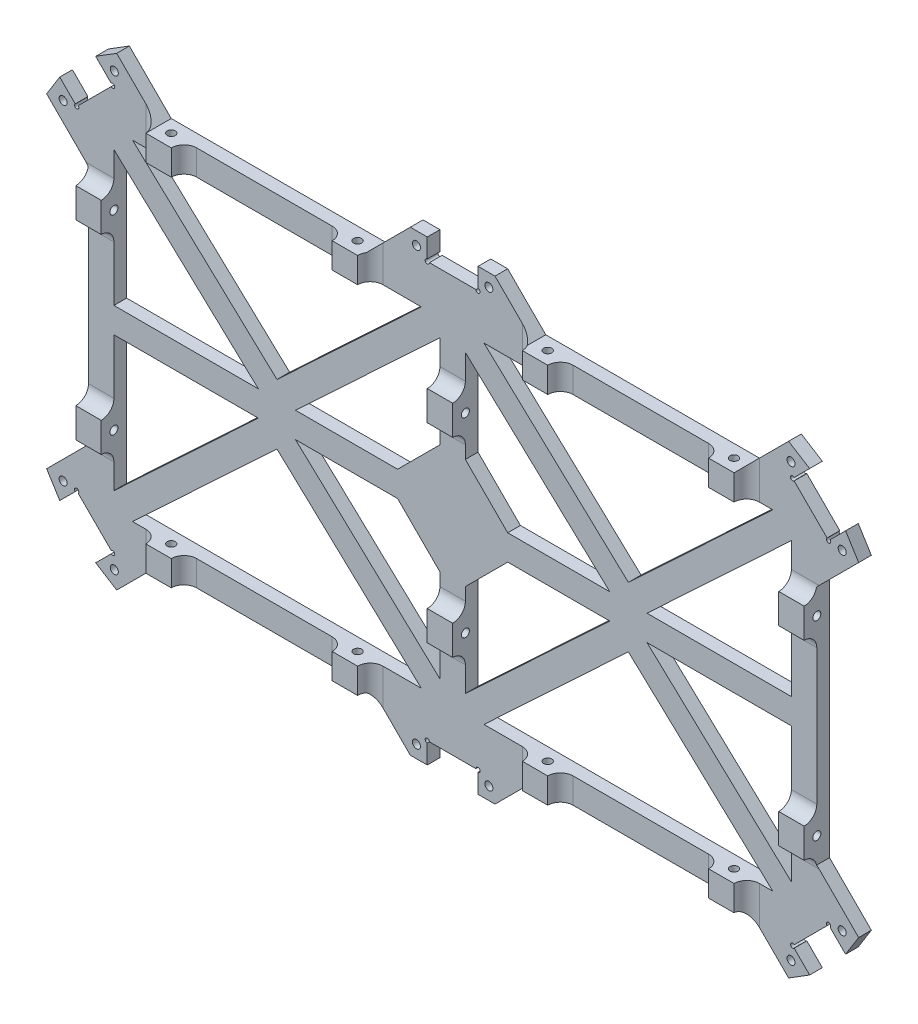
SolidWorks part; units mm, degrees
ref_plane "Plan de face" through (0, 0, 0) normal (0, 0, 1) x (1, 0, 0)
ref_plane "Plan de dessus" through (0, 0, 0) normal (0, 1, 0) x (1, 0, 0)
ref_plane "Plan de droite" through (0, 0, 0) normal (1, 0, 0) x (0, 0, -1)
sketch "Esquisse1" plane through (0, 0, 0) normal (0, 0, 1) x (1, 0, 0)
  line L0 (-86, 45) -> (86, 45)
  line L1 (-75.6076, 39) -> (-7.3924, 39)
  line L2 (-80, 34.8928) -> (-80, 3)
  line L3 (-75.6076, -39) -> (-7.3924, -39)
  line L4 (80, 34.8928) -> (80, 3)
  line L5 (86, 45) -> (86, -45)
  line L6 (-86, -45) -> (86, -45)
  line L7 (-86, 45) -> (-86, -45)
  line L8 (-80, 0) -> (80, 0) construction
  line L9 (-80, 3) -> (-45.8924, 3)
  line L10 (-3, -34.8928) -> (-3, -3)
  line L11 (0, 39) -> (0, -39) construction
  line L12 (-3, 34.8928) -> (-3, 3)
  line L13 (-37.1076, -3) -> (-3, -3)
  line L14 (-10, 45) -> (-10, 39) construction
  line L15 (10, 45) -> (10, 39) construction
  line L16 (-80, 39) -> (-41.5, 3) construction
  line L17 (-60.75, 21) -> (-58.701, 23.1913) construction
  line L18 (-58.701, 23.1913) -> (-75.6076, 39)
  line L19 (-80, -3) -> (-45.8924, -3)
  line L20 (-60.75, -21) -> (-62.799, -18.8087) construction
  line L21 (-60.75, -21) -> (-58.701, -23.1913) construction
  line L22 (-80, -39) -> (-41.5, -3) construction
  line L23 (-58.8571, 23.3372) -> (-41.5, 7.1072)
  line L24 (-60.75, 21) -> (-62.799, 18.8087) construction
  line L25 (-62.799, 18.8087) -> (-80, 34.8928)
  line L26 (-62.799, 18.8087) -> (-45.8924, 3)
  line L27 (-37.1076, 3) -> (-3, 3)
  line L28 (-62.799, -18.8087) -> (-45.8924, -3)
  line L29 (-62.799, -18.8087) -> (-80, -34.8928)
  line L30 (-58.8571, -23.3372) -> (-41.5, -7.1072)
  line L31 (-58.701, -23.1913) -> (-75.6076, -39)
  line L32 (3, 34.8928) -> (3, 3)
  line L33 (3, -34.8928) -> (3, -3)
  line L34 (80, -39) -> (41.5, -3) construction
  line L35 (60.75, -21) -> (58.701, -23.1913) construction
  line L36 (60.75, -21) -> (62.799, -18.8087) construction
  line L37 (58.701, -23.1913) -> (75.6076, -39)
  line L38 (58.8571, -23.3372) -> (41.5, -7.1072)
  line L39 (62.799, -18.8087) -> (80, -34.8928)
  line L40 (62.799, -18.8087) -> (45.8924, -3)
  line L41 (80, -3) -> (45.8924, -3)
  line L42 (37.1076, -3) -> (3, -3)
  line L43 (37.1076, 3) -> (3, 3)
  line L44 (80, 3) -> (45.8924, 3)
  line L45 (60.75, 21) -> (62.799, 18.8087) construction
  line L46 (60.75, 21) -> (58.701, 23.1913) construction
  line L47 (80, 39) -> (41.5, 3) construction
  line L48 (62.799, 18.8087) -> (45.8924, 3)
  line L49 (62.799, 18.8087) -> (80, 34.8928)
  line L50 (58.8571, 23.3372) -> (41.5, 7.1072)
  line L51 (58.701, 23.1913) -> (75.6076, 39)
  line L52 (7.3924, -39) -> (75.6076, -39)
  line L53 (7.3924, 39) -> (75.6076, 39)
  line L54 (-80, -39) -> (80, -39) construction
  line L55 (-80, -3) -> (-80, -34.8928)
  line L56 (-80, 39) -> (80, 39) construction
  line L57 (80, -3) -> (80, -34.8928)
  line L58 (-80, 39) -> (-80, -39) construction
  line L59 (-3, 39) -> (-41.5, 3) construction
  line L60 (80, 39) -> (80, -39) construction
  line L61 (-36.5997, 7.5821) -> (-34.5507, 5.3908) construction
  line L62 (-36.5997, 7.5821) -> (-38.6487, 9.7734) construction
  line L63 (-34.5507, 5.3908) -> (-3, 34.8928)
  line L64 (-34.5507, 5.3908) -> (-37.1076, 3)
  line L65 (-34.5507, 5.3908) -> (-37.1076, 3)
  line L66 (-34.5507, 5.3908) -> (-37.1076, 3)
  line L67 (-41.5, -3) -> (-3, -39) construction
  line L68 (-41.5, 7.1072) -> (-7.3924, 39)
  line L69 (-37.1076, -3) -> (-3, -34.8928)
  line L70 (41.5, -3) -> (3, -39) construction
  line L71 (41.5, -7.1072) -> (7.3924, -39)
  line L72 (-41.5, -7.1072) -> (-7.3924, -39)
  line L73 (37.1076, -3) -> (3, -34.8928)
  line L74 (3, 39) -> (41.5, 3) construction
  line L75 (41.5, 7.1072) -> (7.3924, 39)
  line L76 (34.5507, 5.3908) -> (3, 34.8928)
  line L77 (34.5507, 5.3908) -> (37.1076, 3)
  dimension "D6" = 3
  dimension "D1" = 78
  dimension "D2" = 160
  dimension "D3" = 80
  dimension "D4" = 39
  dimension "D7" = 3
  dimension "D8" = 3
  dimension "D9" = 3
  dimension "D10" = 10
  dimension "D11" = 10
  dimension "D12" = 3
  dimension "D13" = 38.5
  dimension "D14" = 3
  dimension "D15" = 3
  dimension "D5" = 6
extrude "Boss.-Extru.1" add sketch "Esquisse1" along normal blind 3 contours L0 L7 L6 L5 L55 L19 L28 L29 L52 L33 L42 L38 L37 L31 L30 L13 L10 L3 L27 L23 L18 L1 L12 L25 L26 L9 L2 L48 L49 L4 L44 L32 L53 L51 L50 L43 L41 L57 L39
sketch "Esquisse2" plane through (0, 0, 3) normal (0, 0, 1) x (1, 0, 0)
  line L0 (-13, -3) -> (-3, -13)
  line L1 (-37.1076, -3) -> (-3, -3) construction
  line L2 (-3, -34.8928) -> (-3, -3) construction
  line L3 (-13, -3) -> (-13, 3)
  line L4 (-37.1076, 3) -> (-3, 3) construction
  line L5 (-13, 3) -> (-3, 13)
  line L6 (-3, 34.8928) -> (-3, 3) construction
  line L7 (-3, 13) -> (3, 13)
  line L8 (3, 34.8928) -> (3, 3) construction
  line L9 (3, 13) -> (13, 3)
  line L10 (37.1076, 3) -> (3, 3) construction
  line L11 (13, 3) -> (13, -3)
  line L12 (37.1076, -3) -> (3, -3) construction
  line L13 (13, -3) -> (3, -13)
  line L14 (3, -34.8928) -> (3, -3) construction
  line L15 (3, -13) -> (-3, -13)
  line L16 (0, 45) -> (0, -45) construction
  line L17 (-86, 45) -> (86, 45) construction
  line L18 (-86, -45) -> (86, -45) construction
  line L19 (-10.3, 45) -> (-10.3, 39)
  line L20 (-75.6076, 39) -> (-7.3924, 39) construction
  line L21 (10.3, 45) -> (10.3, 39)
  line L22 (7.3924, 39) -> (75.6076, 39) construction
  line L23 (0, 45) -> (0, 54) construction
  line L24 (-11.55, 39) -> (-11.55, 45) construction
  line L25 (0, 54) -> (-10, 54)
  line L26 (0, 54) -> (10, 54)
  line L27 (10, 54) -> (19, 45)
  line L28 (-10, 54) -> (-19, 45)
  line L29 (-86, 0) -> (86, 0) construction
  line L30 (-86, 45) -> (-86, -45) construction
  line L31 (86, 45) -> (86, -45) construction
  line L32 (10, -54) -> (19, -45)
  line L33 (-10, -54) -> (-19, -45)
  line L34 (0, -54) -> (10, -54)
  line L35 (0, -54) -> (-10, -54)
  line L36 (-86, 45) -> (-110.1085, 69.1085) construction
  line L37 (-85.9542, 44.9542) -> (-99.2144, 31.694) construction
  line L38 (-85.9542, 44.9542) -> (-79.9085, 51) construction
  line L39 (-79.3417, 54.888) -> (-69.4537, 45)
  line L40 (-89.5355, 48.5355) -> (-79.3417, 54.888)
  line L41 (-95.888, 38.3417) -> (-86, 28.4537)
  line L42 (-89.5355, 48.5355) -> (-95.888, 38.3417)
  line L43 (79.3417, 54.888) -> (69.4537, 45)
  line L44 (89.5355, 48.5355) -> (79.3417, 54.888)
  line L45 (89.5355, 48.5355) -> (95.888, 38.3417)
  line L46 (95.888, 38.3417) -> (86, 28.4537)
  line L47 (95.888, -38.3417) -> (86, -28.4537)
  line L48 (89.5355, -48.5355) -> (95.888, -38.3417)
  line L49 (89.5355, -48.5355) -> (79.3417, -54.888)
  line L50 (79.3417, -54.888) -> (69.4537, -45)
  line L51 (-79.3417, -54.888) -> (-69.4537, -45)
  line L52 (-89.5355, -48.5355) -> (-79.3417, -54.888)
  line L53 (-89.5355, -48.5355) -> (-95.888, -38.3417)
  line L54 (-95.888, -38.3417) -> (-86, -28.4537)
  circle A0 centre (8.55, 51) radius 0.95
  circle A1 centre (-8.55, 51) radius 0.95
  circle A3 centre (8.55, -51) radius 0.95
  circle A4 centre (-8.55, -51) radius 0.95
  circle A7 centre (-92, 38.9085) radius 0.95
  circle A8 centre (-79.9085, 51) radius 0.95
  circle A9 centre (79.9085, 51) radius 0.95
  circle A10 centre (92, 38.9085) radius 0.95
  circle A12 centre (92, -38.9085) radius 0.95
  circle A14 centre (79.9085, -51) radius 0.95
  circle A15 centre (-79.9085, -51) radius 0.95
  circle A17 centre (-92, -38.9085) radius 0.95
  point P36 (-10.3, 42)
  dimension "D5" = 1.75
  dimension "D6" = 1.9
  dimension "D7" = 1.9
  dimension "D23" = 8.55
  dimension "D25" = 1.9
  dimension "D27" = 1.9
  dimension "D28" = 90
  dimension "D1" = 10
  dimension "D2" = 10
  dimension "D3" = 10.3
  dimension "D4" = 10.3
  dimension "D8" = 1.75
  dimension "D9" = 3
  dimension "D12" = 3
  dimension "D13" = 9
  dimension "D14" = 3
  dimension "D15" = 10
  dimension "D16" = 10
  dimension "D17" = 45
  dimension "D18" = 45
  dimension "D19" = 135
  dimension "D20" = 90
  dimension "D21" = 3
  dimension "D26" = 8.55
  dimension "D29" = 45
  dimension "D30" = 3.15
  dimension "D31" = 0
  dimension "D32" = 5
extrude "Boss.-Extru.2" add sketch "Esquisse2" against normal up to surface (3 mm away)
sketch "Esquisse6" plane through (0, 0, 3) normal (0, 0, 1) x (1, 0, 0)
  line L0 (-86, 0) -> (86, 0) construction
  line L1 (-86, 28.4537) -> (-86, -28.4537) construction
  line L2 (-86, -19) -> (-80, -19)
  line L4 (-80, -3) -> (-80, -34.8928) construction
  line L5 (-86, -19) -> (-86, -26)
  line L6 (-86, -26) -> (-80, -26)
  line L7 (-80, -26) -> (-80, -19)
  line L8 (-80, 26) -> (-80, 19)
  line L9 (-86, 26) -> (-80, 26)
  line L10 (-86, 19) -> (-86, 26)
  line L11 (-86, 19) -> (-80, 19)
  line L12 (0, 54) -> (0, -54) construction
  line L13 (80, -26) -> (80, -19)
  line L14 (86, -26) -> (80, -26)
  line L15 (86, -19) -> (86, -26)
  line L16 (86, -19) -> (80, -19)
  line L17 (86, 19) -> (80, 19)
  line L18 (86, 19) -> (86, 26)
  line L19 (86, 26) -> (80, 26)
  line L20 (80, 26) -> (80, 19)
  line L21 (-69.4537, 45) -> (-19, 45) construction
  line L22 (-69.4537, 45) -> (-63.4537, 45)
  line L23 (-69.4537, 45) -> (-69.4537, 39)
  line L24 (-69.4537, 39) -> (-63.4537, 39)
  line L25 (-63.4537, 45) -> (-63.4537, 39)
  line L26 (-75.6076, 39) -> (-7.3924, 39) construction
  line L27 (19.4537, 45) -> (19.4537, 39)
  line L28 (-25.4537, 45) -> (-19.4537, 45)
  line L29 (-25.4537, 45) -> (-25.4537, 39)
  line L30 (-25.4537, 39) -> (-19.4537, 39)
  line L31 (-19.4537, 45) -> (-19.4537, 39)
  line L32 (25.4537, 39) -> (19.4537, 39)
  line L33 (25.4537, 45) -> (25.4537, 39)
  line L34 (25.4537, 45) -> (19.4537, 45)
  line L35 (63.4537, 45) -> (63.4537, 39)
  line L36 (69.4537, 39) -> (63.4537, 39)
  line L37 (69.4537, 45) -> (69.4537, 39)
  line L38 (69.4537, 45) -> (63.4537, 45)
  line L39 (69.4537, -45) -> (63.4537, -45)
  line L40 (69.4537, -45) -> (69.4537, -39)
  line L41 (69.4537, -39) -> (63.4537, -39)
  line L42 (63.4537, -45) -> (63.4537, -39)
  line L43 (25.4537, -45) -> (19.4537, -45)
  line L44 (25.4537, -45) -> (25.4537, -39)
  line L45 (25.4537, -39) -> (19.4537, -39)
  line L46 (-19.4537, -45) -> (-19.4537, -39)
  line L47 (-25.4537, -39) -> (-19.4537, -39)
  line L48 (-25.4537, -45) -> (-25.4537, -39)
  line L49 (-25.4537, -45) -> (-19.4537, -45)
  line L50 (19.4537, -45) -> (19.4537, -39)
  line L51 (-63.4537, -45) -> (-63.4537, -39)
  line L52 (-69.4537, -39) -> (-63.4537, -39)
  line L53 (-69.4537, -45) -> (-69.4537, -39)
  line L54 (-69.4537, -45) -> (-63.4537, -45)
  line L55 (-3, 34.8928) -> (-3, 13) construction
  line L56 (-3, 26) -> (3, 26)
  line L57 (-3, 26) -> (-3, 19)
  line L58 (-3, 19) -> (3, 19)
  line L59 (3, 26) -> (3, 19)
  line L60 (3, 34.8928) -> (3, 13) construction
  line L61 (-3, -34.8928) -> (-3, -13) construction
  line L62 (-3, -26) -> (3, -26)
  line L63 (-3, -26) -> (-3, -19)
  line L64 (-3, -19) -> (3, -19)
  line L65 (3, -26) -> (3, -19)
  line L66 (3, -34.8928) -> (3, -13) construction
  dimension "D1" = 19
  dimension "D2" = 7
  dimension "D3" = 6
  dimension "D4" = 6
  dimension "D5" = 38
  dimension "D6" = 0
  dimension "D7" = 7
  dimension "D8" = 7
extrude "Boss.-Extru.4" add sketch "Esquisse6" along normal blind 3
sketch "Esquisse7" plane through (0, -45, 0) normal (0, -1, 0) x (1, 0, 0)
  line L0 (-69.4537, 0) -> (-63.4537, 6) construction
  line L1 (-25.4537, 6) -> (-25.4537, 0) construction
  line L2 (-25.4537, 6) -> (-25.4537, 3) construction
  line L3 (-69.4537, 0) -> (-19, 0) construction
  line L4 (-25.4537, 0) -> (-19.4537, 6) construction
  line L5 (25.4537, 6) -> (25.4537, 0) construction
  line L6 (19, 0) -> (69.4537, 0) construction
  line L7 (19.4537, 6) -> (25.4537, 0) construction
  line L8 (69.4537, 0) -> (63.4537, 6) construction
  circle A0 centre (-66.4537, 3) radius 0.95
  circle A1 centre (-22.4537, 3) radius 0.95
  circle A2 centre (22.4537, 3) radius 0.95
  circle A3 centre (66.4537, 3) radius 0.95
  dimension "D1" = 1.9
  dimension "D2" = 1.9
  dimension "D3" = 1.9
  dimension "D4" = 1.9
extrude "Enlèv. mat.-Extru.3" cut sketch "Esquisse7" against normal up to next
sketch "Esquisse8" plane through (0, 45, 0) normal (0, 1, 0) x (1, 0, 0)
  line L0 (-63.4537, -6) -> (-69.4537, 0) construction
  line L1 (-25.4537, -6) -> (-25.4537, 0) construction
  line L2 (-69.4537, 0) -> (-19, 0) construction
  line L3 (-25.4537, 0) -> (-19.4537, -6) construction
  line L4 (19.4537, -6) -> (19.4537, 0) construction
  line L5 (19, 0) -> (69.4537, 0) construction
  line L6 (19.4537, 0) -> (25.4537, -6) construction
  line L7 (63.4537, -6) -> (69.4537, 0) construction
  circle A0 centre (66.4537, -3) radius 0.95
  circle A1 centre (22.4537, -3) radius 0.95
  circle A2 centre (-22.4537, -3) radius 0.95
  circle A3 centre (-66.4537, -3) radius 0.95
  dimension "D1" = 1.9
  dimension "D2" = 1.9
  dimension "D3" = 1.9
  dimension "D4" = 1.9
extrude "Enlèv. mat.-Extru.4" cut sketch "Esquisse8" against normal up to next
fillet "Congé2" radius 3 80 edges at (-86, -19, 4.5) (-83, -26, 3) (-86, -26, 4.5) (-80, -26, 4.5) (-83, -19, 3) (-80, -19, 4.5) (-83, 26, 3) (-80, 26, 4.5) (-86, 26, 4.5) (-83, 19, 3) (-86, 19, 4.5) (-80, 19, 4.5) (83, -26, 3) (80, -26, 4.5) (86, -26, 4.5) (83, -19, 3) (86, -19, 4.5) (80, -19, 4.5) (86, 19, 4.5) (83, 26, 3) (86, 26, 4.5) (80, 26, 4.5) (83, 19, 3) (80, 19, 4.5) (-69.4537, 42, 3) (-69.4537, 39, 4.5) (-63.4537, 42, 3) (-63.4537, 39, 4.5) (-63.4537, 45, 4.5) (-25.4537, 42, 3) (-25.4537, 45, 4.5) (-25.4537, 39, 4.5) (-19.4537, 42, 3) (-19.4537, 39, 4.5) (-19.4537, 45, 4.5) (25.4537, 45, 4.5) (19.4537, 42, 3) (19.4537, 45, 4.5) (19.4537, 39, 4.5) (25.4537, 42, 3) (25.4537, 39, 4.5) (63.4537, 42, 3) (63.4537, 45, 4.5) (63.4537, 39, 4.5) (69.4537, 42, 3) (69.4537, 39, 4.5) (69.4537, -42, 3) (69.4537, -39, 4.5) (63.4537, -42, 3) (63.4537, -39, 4.5) (63.4537, -45, 4.5) (25.4537, -42, 3) (25.4537, -45, 4.5) (25.4537, -39, 4.5) (19.4537, -42, 3) (19.4537, -39, 4.5) (19.4537, -45, 4.5) (-25.4537, -45, 4.5) (-19.4537, -42, 3) (-19.4537, -45, 4.5) (-19.4537, -39, 4.5) (-25.4537, -42, 3) (-25.4537, -39, 4.5) (-63.4537, -42, 3) (-63.4537, -45, 4.5) (-63.4537, -39, 4.5) (-69.4537, -42, 3) (-69.4537, -39, 4.5) (-3, 26, 4.5) (0, 19, 3) (-3, 19, 4.5) (3, 19, 4.5) (0, 26, 3) (3, 26, 4.5) (-3, -19, 4.5) (0, -26, 3) (-3, -26, 4.5) (3, -26, 4.5) (0, -19, 3) (3, -19, 4.5)
sketch "Esquisse9" plane through (-86, 0, 0) normal (-1, 0, 0) x (0, 0, 1)
  line L0 (6, 26) -> (0, 26) construction
  line L1 (0, 28.4537) -> (0, -28.4537) construction
  line L2 (0, 26) -> (6, 19) construction
  line L3 (6, -19) -> (0, -19) construction
  line L4 (0, -19) -> (6, -26) construction
  arc A0 (3, -16) -> (6, -19) centre (6, -16) ccw construction
  circle A1 centre (3, -22.5) radius 0.95
  circle A2 centre (3, 22.5) radius 0.95
  dimension "D1" = 1.9
  dimension "D2" = 1.9
extrude "Enlèv. mat.-Extru.5" cut sketch "Esquisse9" against normal up to next
sketch "Esquisse10" plane through (-3, 0, 0) normal (-1, 0, 0) x (0, 0, 1)
  line L0 (6, 26) -> (0, 26) construction
  line L2 (0, 26) -> (6, 19) construction
  line L3 (6, -19) -> (0, -19) construction
  line L4 (0, -34.8928) -> (0, -13) construction
  line L5 (0, -19) -> (6, -26) construction
  line L6 (0, 34.8928) -> (0, 13) construction
  arc A0 (3, 29) -> (6, 26) centre (6, 29) ccw construction
  circle A1 centre (3, -22.5) radius 0.95
  circle A2 centre (3, 22.5) radius 0.95
  dimension "D1" = 1.9
  dimension "D2" = 1.9
extrude "Enlèv. mat.-Extru.6" cut sketch "Esquisse10" against normal up to next
sketch "Esquisse11" plane through (80, 0, 0) normal (-1, 0, 0) x (0, 0, 1)
  line L0 (6, -19) -> (0, -18.9464) construction
  line L1 (0, -3) -> (0, -34.8928) construction
  line L2 (0, -18.9464) -> (6, -26) construction
  line L3 (6, 26) -> (0, 26) construction
  line L4 (0, 34.8928) -> (0, 3) construction
  line L5 (0, 26) -> (6, 19) construction
  circle A0 centre (3, 22.5) radius 0.95
  circle A1 centre (3, -22.4732) radius 0.95
  dimension "D1" = 1.9
  dimension "D2" = 1.9
extrude "Enlèv. mat.-Extru.7" cut sketch "Esquisse11" against normal up to next
sketch "Esquisse12" plane through (0, 0, 3) normal (0, 0, 1) x (1, 0, 0)
  line L0 (-92, -38.9085) -> (-79.9085, -51) construction
  line L1 (-89.6498, -36.5582) -> (-92, -38.9085) construction
  line L2 (-79.9085, -51) -> (-77.6111, -48.7026) construction
  line L3 (-90.5858, -37.4943) -> (-78.4943, -49.5858) construction
  line L4 (-84.54, -43.54) -> (-83.1692, -42.1692) construction
  line L5 (-83.1692, -42.1692) -> (-87.4118, -37.9265) construction
  line L6 (-87.4118, -37.9265) -> (-88.7827, -39.2974) construction
  line L7 (-88.7827, -39.2974) -> (-80.2974, -47.7827)
  line L8 (-80.2974, -47.7827) -> (-86.6613, -54.1466)
  line L9 (-88.7827, -39.2974) -> (-95.1466, -45.6613)
  line L10 (-95.1466, -45.6613) -> (-86.6613, -54.1466)
  line L11 (-8.55, -51) -> (8.55, -51) construction
  line L12 (-6, -49) -> (6, -49) construction
  line L13 (0, -51) -> (0, -49) construction
  line L14 (87.4118, -37.9265) -> (88.7827, -39.2974) construction
  line L15 (-6, -49) -> (6, -49)
  line L16 (-6, -49) -> (-6, -56.1929)
  line L17 (-6, -56.1929) -> (6, -56.1929)
  line L18 (6, -49) -> (6, -56.1929)
  line L19 (83.1692, -42.1692) -> (87.4118, -37.9265) construction
  line L20 (84.54, -43.54) -> (83.1692, -42.1692) construction
  line L21 (90.5858, -37.4943) -> (78.4943, -49.5858) construction
  line L22 (79.9085, -51) -> (77.6111, -48.7026) construction
  line L23 (89.6498, -36.5582) -> (92, -38.9085) construction
  line L24 (92, -38.9085) -> (79.9085, -51) construction
  line L25 (95.1466, -45.6613) -> (86.6613, -54.1466)
  line L26 (88.7827, -39.2974) -> (95.1466, -45.6613)
  line L27 (80.2974, -47.7827) -> (86.6613, -54.1466)
  line L28 (88.7827, -39.2974) -> (80.2974, -47.7827)
  line L29 (-86, 0) -> (86, 0) construction
  line L30 (86, 16) -> (86, -16) construction
  line L31 (92, 38.9085) -> (79.9085, 51) construction
  line L32 (89.6498, 36.5582) -> (92, 38.9085) construction
  line L33 (79.9085, 51) -> (77.6111, 48.7026) construction
  line L34 (90.5858, 37.4943) -> (78.4943, 49.5858) construction
  line L35 (84.54, 43.54) -> (83.1692, 42.1692) construction
  line L36 (83.1692, 42.1692) -> (87.4118, 37.9265) construction
  line L37 (87.4118, 37.9265) -> (88.7827, 39.2974) construction
  line L38 (0, 51) -> (0, 49) construction
  line L39 (-6, 49) -> (6, 49) construction
  line L40 (-8.55, 51) -> (8.55, 51) construction
  line L41 (-87.4118, 37.9265) -> (-88.7827, 39.2974) construction
  line L42 (-83.1692, 42.1692) -> (-87.4118, 37.9265) construction
  line L43 (-84.54, 43.54) -> (-83.1692, 42.1692) construction
  line L44 (-90.5858, 37.4943) -> (-78.4943, 49.5858) construction
  line L45 (-79.9085, 51) -> (-77.6111, 48.7026) construction
  line L46 (-89.6498, 36.5582) -> (-92, 38.9085) construction
  line L47 (-92, 38.9085) -> (-79.9085, 51) construction
  line L48 (88.7827, 39.2974) -> (80.2974, 47.7827)
  line L49 (80.2974, 47.7827) -> (86.6613, 54.1466)
  line L50 (88.7827, 39.2974) -> (95.1466, 45.6613)
  line L51 (95.1466, 45.6613) -> (86.6613, 54.1466)
  line L52 (6, 49) -> (6, 56.1929)
  line L53 (-6, 56.1929) -> (6, 56.1929)
  line L54 (-6, 49) -> (-6, 56.1929)
  line L55 (-6, 49) -> (6, 49)
  line L56 (-95.1466, 45.6613) -> (-86.6613, 54.1466)
  line L57 (-88.7827, 39.2974) -> (-95.1466, 45.6613)
  line L58 (-80.2974, 47.7827) -> (-86.6613, 54.1466)
  line L59 (-88.7827, 39.2974) -> (-80.2974, 47.7827)
  dimension "D1" = 90
  dimension "D2" = 90
  dimension "D3" = 2
  dimension "D4" = 2
  dimension "D5" = 6
  dimension "D6" = 12
  dimension "D7" = 90
  dimension "D8" = 9
  dimension "D9" = 2
  dimension "D10" = 6
extrude "Enlèv. mat.-Extru.8" cut sketch "Esquisse12" against normal up to next
sketch "Esquisse13" plane through (0, 0, 3) normal (0, 0, 1) x (1, 0, 0)
  circle A0 centre (-6, -49) radius 0.5
  circle A1 centre (6, -49) radius 0.5
  circle A2 centre (80.2974, -47.7827) radius 0.5
  circle A3 centre (88.7827, -39.2974) radius 0.5
  circle A4 centre (-88.7827, -39.2974) radius 0.5
  circle A5 centre (-80.2974, -47.7827) radius 0.5
  circle A6 centre (-80.2974, 47.7827) radius 0.5
  circle A7 centre (-88.7827, 39.2974) radius 0.5
  circle A8 centre (88.7827, 39.2974) radius 0.5
  circle A9 centre (80.2974, 47.7827) radius 0.5
  circle A10 centre (6, 49) radius 0.5
  circle A11 centre (-6, 49) radius 0.5
  dimension "D1" = 1
  dimension "D2" = 1
  dimension "D3" = 1
  dimension "D4" = 1
  dimension "D5" = 1
  dimension "D6" = 1
extrude "Enlèv. mat.-Extru.9" cut sketch "Esquisse13" against normal up to next
